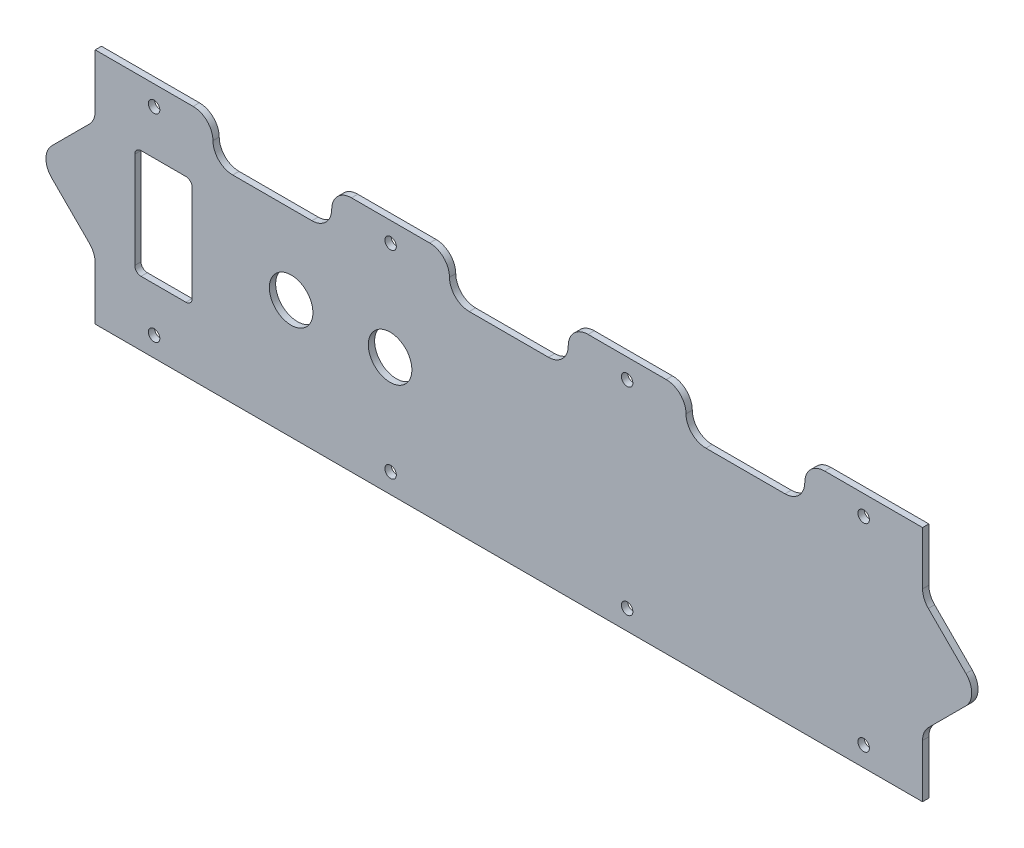
SolidWorks part; units mm, degrees
ref_plane "Front Plane" through (0, 0, 0) normal (0, 0, 1) x (1, 0, 0)
ref_plane "Top Plane" through (0, 0, 0) normal (0, 1, 0) x (1, 0, 0)
ref_plane "Right Plane" through (0, 0, 0) normal (1, 0, 0) x (0, 0, -1)
sketch "Sketch2" plane through (0, 0, 0) normal (0, 0, 1) x (1, 0, 0)
  line L1 (0, 0) -> (540, 0)
  line L2 (0, 0) -> (0, 120)
  line L3 (0, 120) -> (540, 120)
  line L4 (540, 0) -> (540, 120)
  dimension "D1" = 540
  dimension "D2" = 120
extrude "Boss-Extrude1" add sketch "Sketch2" along normal blind 3.175
sketch "Sketch3" plane through (0, 0, 3.175) normal (0, 0, 1) x (1, 0, 0)
  line L0 (540, 120) -> (0, 120) construction
  line L1 (0, 0) -> (61, 0)
  line L2 (0, 0) -> (0, 120)
  line L3 (0, 120) -> (61, 120)
  line L4 (61, 0) -> (61, 31)
  line L5 (61, 89) -> (39.0711, 67.0711)
  line L6 (39.0711, 52.9289) -> (61, 31)
  line L7 (61, 89) -> (61, 120)
  line L8 (0, 0) -> (540, 0) construction
  line L9 (270, 0) -> (270, 120) construction
  line L10 (479, 89) -> (479, 120)
  line L11 (500.9289, 52.9289) -> (479, 31)
  line L12 (479, 89) -> (500.9289, 67.0711)
  line L13 (479, 0) -> (479, 31)
  line L14 (540, 120) -> (479, 120)
  line L15 (540, 0) -> (540, 120)
  line L16 (540, 0) -> (479, 0)
  line L17 (300, 120) -> (300, 100)
  line L18 (120.5, 120) -> (180.5, 120)
  line L19 (120.5, 120) -> (120.5, 100)
  line L20 (120.5, 100) -> (180.5, 100)
  line L21 (180.5, 120) -> (180.5, 100)
  line L22 (240, 120) -> (300, 120)
  line L23 (240, 120) -> (240, 100)
  line L24 (240, 100) -> (300, 100)
  line L25 (419.5, 100) -> (359.5, 100)
  line L26 (359.5, 120) -> (359.5, 100)
  line L27 (419.5, 120) -> (359.5, 120)
  line L28 (419.5, 120) -> (419.5, 100)
  arc A0 (39.0711, 52.9289) -> (39.0711, 67.0711) centre (46.1421, 60) cw
  arc A1 (500.9289, 52.9289) -> (500.9289, 67.0711) centre (493.8579, 60) ccw
  point P12 (32, 60)
  point P25 (508, 60)
  dimension "D3" = 10
  dimension "D1" = 61
  dimension "D2" = 32
  dimension "D4" = 20
  dimension "D5" = 60
  dimension "D6" = 59.5
  dimension "D7" = 59.5
extrude "Cut-Extrude1" cut sketch "Sketch3" against normal through all
fillet "Fillet1" radius 10 4 edges at (479, 31, 1.5875) (479, 89, 1.5875) (61, 31, 1.5875) (61, 89, 1.5875)
fillet "Fillet2" radius 10 12 edges at (419.5, 120, 1.5875) (419.5, 100, 1.5875) (359.5, 100, 1.5875) (359.5, 120, 1.5875) (300, 120, 1.5875) (300, 100, 1.5875) (240, 100, 1.5875) (240, 120, 1.5875) (180.5, 120, 1.5875) (180.5, 100, 1.5875) (120.5, 100, 1.5875) (120.5, 120, 1.5875)
hole_wizard "M5 Clearance Hole1" positions "3DSketch1" profile "Sketch5" hole size "M5" standard "ANSI Metric" end condition through all
sketch3d "3DSketch1"
  line L0 (61, 0, 3.175) -> (479, 0, 3.175) construction
  line L1 (61, 0, 3.175) -> (61, 26.8579, 3.175) construction
  line L2 (90.75, 110, 3.175) -> (90.75, 10, 3.175) construction
  point P0 (90.75, 10, 3.175)
  point P7 (90.75, 110, 3.175)
  dimension "D1" = 10
  dimension "D2" = 29.75
  dimension "D3" = 100
sketch "Sketch5" plane through (90.75, 10, 3.175) normal (1, 0, 0) x (0, -1, 0)
  line L0 (0, 0) -> (0, 3.175)
  line L1 (0, 3.175) -> (2.9, 3.175)
  line L2 (2.9, 3.175) -> (2.9, 0)
  line L5 (2.9, 0) -> (0, 0)
  line L11 (0, -6.35) -> (0, 107.95) construction
  dimension "Thru Hole Dia." = 5.8
  dimension "Thru Hole Depth" = 3.175
pattern_linear "LPattern1" count 4 spacing 119.5 along (1, 0, 0) of "M5 Clearance Hole1"
sketch "Sketch6" plane through (0, 0, 3.175) normal (0, 0, 1) x (1, 0, 0)
  line L0 (61, 120) -> (61, 0) construction
  line L1 (81, 87.5) -> (110, 87.5)
  line L2 (81, 87.5) -> (81, 32.5)
  line L3 (81, 32.5) -> (110, 32.5)
  line L4 (110, 87.5) -> (110, 32.5)
  line L5 (479, 120) -> (479, 0) construction
  line L6 (479, 120) -> (479, 93.1421) construction
  line L7 (61, 60) -> (479, 60) construction
  circle A0 centre (160, 60) radius 11
  circle A1 centre (210, 60) radius 11
  point P15 (81, 60)
  dimension "D4" = 22
  dimension "D1" = 55
  dimension "D2" = 29
  dimension "D3" = 20
  dimension "D5" = 50
  dimension "D6" = 50
extrude "Cut-Extrude2" cut sketch "Sketch6" against normal through all
fillet "Fillet3" radius 3.175 4 edges at (81, 32.5, 1.5875) (110, 32.5, 1.5875) (110, 87.5, 1.5875) (81, 87.5, 1.5875)
